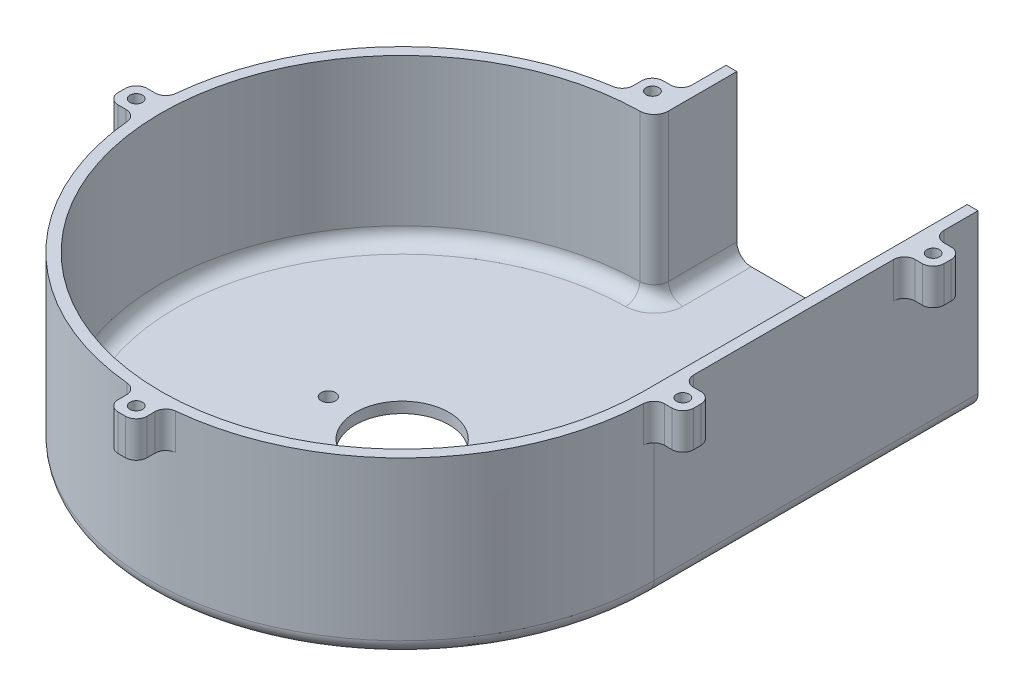
SolidWorks part; units mm, degrees
ref_plane "Front Plane" through (0, 0, 0) normal (0, 0, 1) x (1, 0, 0)
ref_plane "Top Plane" through (0, 0, 0) normal (0, 1, 0) x (1, 0, 0)
ref_plane "Right Plane" through (0, 0, 0) normal (1, 0, 0) x (0, 0, -1)
sketch "Sketch2" plane through (0, 0, 0) normal (0, 1, 0) x (1, 0, 0)
  line L0 (0, 70) -> (70, 70) construction
  line L2 (70, 0) -> (70, 90)
  line L3 (70, 90) -> (0, 90)
  line L4 (0, 70) -> (0, 90)
  circle A0 centre (0, 0) radius 59 construction
  arc A1 (0, 70) -> (70, 0) centre (0, 0) ccw
  circle A2 centre (0, 0) radius 20.5 construction
  circle A3 centre (20.5, 0) radius 2
  circle A4 centre (-20.5, 0) radius 2
  circle A5 centre (0, 0) radius 13
  dimension "D1" = 118
  dimension "D2" = 70
  dimension "D4" = 4
  dimension "D6" = 26
  dimension "D5" = 41
  dimension "D7" = 20
extrude "Boss-Extrude1" add sketch "Sketch2" along normal blind 3
sketch "Sketch3" plane through (0, 3, 0) normal (0, 1, 0) x (1, 0, 0)
  line L3 (70, 90) -> (0, 90) construction
  line L4 (0, 90) -> (3, 90)
  line L5 (67, 90) -> (70, 90)
  line L6 (67, 0) -> (67, 87)
  line L7 (67, 87) -> (3, 87)
  line L8 (3, 87) -> (3, 66.9328)
  line L9 (67, 0) -> (67, 90)
  line L11 (3, 90) -> (3, 66.9328)
  line L12 (70, 0) -> (70, 90)
  line L13 (70, 90) -> (0, 90)
  line L14 (0, 90) -> (0, 70)
  line L15 (70, 0) -> (70, 90)
  line L17 (0, 90) -> (0, 70)
  arc A2 (3, 66.9328) -> (67, 0) centre (0, 0) ccw
  arc A3 (3, 66.9328) -> (67, 0) centre (0, 0) ccw
  arc A4 (0, 70) -> (70, 0) centre (0, 0) ccw
  arc A5 (0, 70) -> (70, 0) centre (0, 0) ccw
  dimension "D1" = 3
  dimension "D2" = 0
extrude "Boss-Extrude2" add sketch "Sketch3" along normal blind 45
sketch "Sketch4" plane through (0, 48, 0) normal (0, 1, 0) x (1, 0, 0)
  line L0 (-4, 77.5414) -> (-4, 69.5414) construction
  line L1 (0, 77.5414) -> (-8, 77.5414)
  line L2 (0, 77.5414) -> (0, 70)
  line L4 (-8, 77.5414) -> (-8, 69.5414)
  line L5 (70, 77.5414) -> (78, 77.5414)
  line L6 (70, 77.5414) -> (70, 69.5414)
  line L7 (70, 69.5414) -> (78, 69.5414)
  line L8 (78, 77.5414) -> (78, 69.5414)
  line L9 (74, 77.5414) -> (74, 69.5414) construction
  line L10 (0, 70) -> (0, 69.5414) construction
  line L11 (0, 69.5414) -> (-8, 69.5414) construction
  line L13 (70, 0) -> (70, 90) construction
  line L14 (-77.8856, 0) -> (-69.8856, 0) construction
  line L15 (-69.8856, 4) -> (-77.8856, 4)
  line L16 (-69.8856, 4) -> (-69.8856, -4)
  line L17 (-69.8856, -4) -> (-77.8856, -4)
  line L18 (-77.8856, 4) -> (-77.8856, -4)
  line L19 (0, -69.8856) -> (0, -77.8856) construction
  line L20 (-4, -69.8856) -> (4, -69.8856)
  line L21 (-4, -69.8856) -> (-4, -77.8856)
  line L22 (-4, -77.8856) -> (4, -77.8856)
  line L23 (4, -69.8856) -> (4, -77.8856)
  line L24 (78, 4) -> (70, 4) construction
  line L25 (70, 0) -> (78, 0)
  line L26 (70, 0) -> (70, 8)
  line L27 (70, 8) -> (78, 8)
  line L28 (78, 0) -> (78, 8)
  circle A0 centre (-4, 73.5414) radius 1.75
  circle A1 centre (74, 73.5414) radius 1.75
  arc A2 (0, 70) -> (70, 0) centre (0, 0) ccw construction
  circle A3 centre (-73.8856, 0) radius 1.75
  circle A4 centre (0, -73.8856) radius 1.75
  circle A5 centre (74, 4) radius 1.75
  arc M8 (0, 70) -> (70, 0) centre (0, 0) ccw
  line M9 (70, 0) -> (70, 90)
  line M15 (0, 90) -> (0, 70)
  dimension "D5" = 3.5
  dimension "D6" = 3.5
  dimension "D8" = 3.5
  dimension "D10" = 3.5
  dimension "D12" = 3.5
  dimension "D1" = 8
  dimension "D2" = 8
  dimension "D3" = 8
  dimension "D4" = 8
  dimension "D7" = 8
  dimension "D9" = 8
  dimension "D11" = 8
extrude "Boss-Extrude3" add sketch "Sketch4" against normal blind 10 contours L23 L21 L22 A4 M8 | L15 L18 L17 A3 M8 | L25 L28 L27 A5 M9 | L8 L5 L7 A1 M9 | L1 L4 A0 M8 M15 region at (-0.1131, 48, -73.7707) region at (70.1131, 48, -73.5414) region at (70.1131, 48, -4) region at (0, 48, 70.1131) region at (-70.1131, 48, 0)
fillet "Fillet1" radius 3 19 edges at (70, 43, -77.5414) (78, 43, -77.5414) (78, 43, -69.5414) (70, 43, -69.5414) (70, 43, -8) (78, 43, -8) (78, 43, 0) (70, 43, 0) (4, 43, 69.8856) (4, 43, 77.8856) (-4, 43, 77.8856) (-4, 43, 69.8856) (-69.8856, 43, 4) (-77.8856, 43, 4) (-77.8856, 43, -4) (-69.8856, 43, -4) (-8, 43, -69.5414) (0, 43, -77.5414) (-8, 43, -77.5414)
fillet "Fillet2" radius 4 1 edges at (3, 25.5, -66.9328)
fillet "Fillet3" radius 4 4 edges at (67, 3, -45) (3, 3, -80.4965) (1.8483, 3, -68.1845) (-47.0413, 3, 47.7086)
fillet "Fillet4" radius 4 4 edges at (-49.4975, 0, 49.4975) (70, 0, -45) (0, 19, -70) (0, 0, -80)
